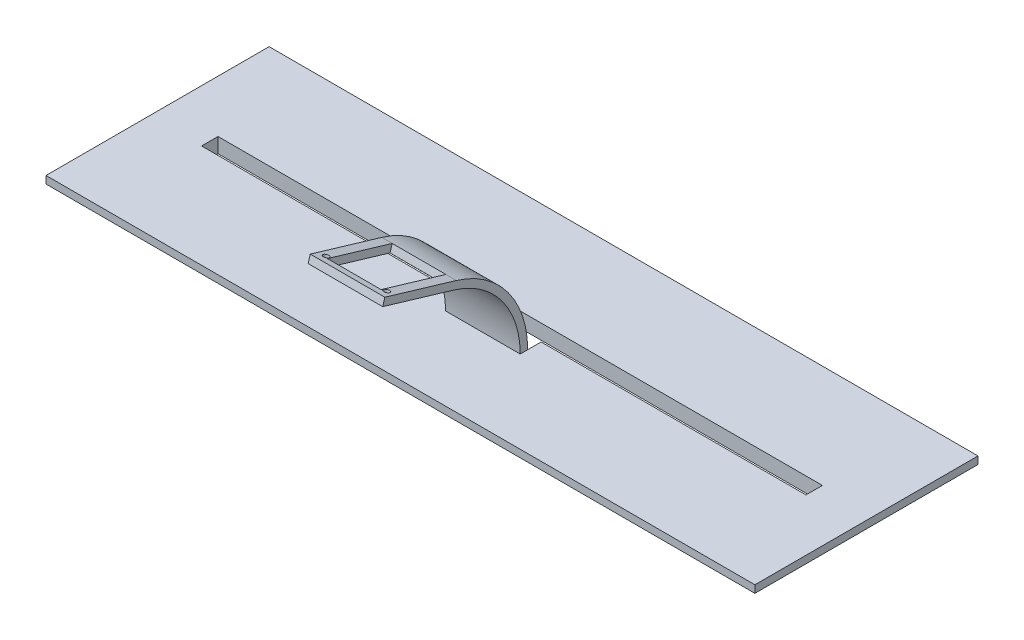
SolidWorks part; units mm, degrees
ref_plane "Front" through (0, 0, 0) normal (0, 0, 1) x (1, 0, 0)
ref_plane "Top" through (0, 0, 0) normal (0, 1, 0) x (1, 0, 0)
ref_plane "Right" through (0, 0, 0) normal (1, 0, 0) x (0, 0, -1)
sketch "Sketch1" plane through (0, 0, 0) normal (0, 1, 0) x (1, 0, 0)
  line L1 (-117.475, 34.798) -> (117.475, 34.798)
  line L2 (-117.475, 34.798) -> (-117.475, -34.798)
  line L3 (-117.475, -34.798) -> (117.475, -34.798)
  line L4 (117.475, 34.798) -> (117.475, -34.798)
  line L5 (-117.475, 34.798) -> (117.475, -34.798) construction
  line L6 (-117.475, -34.798) -> (117.475, 34.798) construction
  point P0 (0, 0)
  dimension "D1" = 69.596
  dimension "D2" = 234.95
extrude "Boss-Extrude1" add sketch "Sketch1" along normal blind 2.54
sketch "Sketch2" plane through (0, 2.54, 0) normal (0, 1, 0) x (1, 0, 0)
  line L8 (120.65, -37.973) -> (120.65, 37.973)
  line L9 (120.65, 37.973) -> (-120.65, 37.973)
  line L10 (-120.65, 37.973) -> (-120.65, -37.973)
  line L11 (-120.65, -37.973) -> (120.65, -37.973)
  line L12 (120.65, -37.973) -> (120.65, 37.973)
  line L13 (120.65, 37.973) -> (-120.65, 37.973)
  line L14 (-120.65, 37.973) -> (-120.65, -37.973)
  line L15 (-120.65, -37.973) -> (120.65, -37.973)
  dimension "D1" = 3.175
extrude "Boss-Extrude2" add sketch "Sketch2" along normal blind 2.54
sketch "Sketch3" plane through (0, 5.08, 0) normal (0, 1, 0) x (1, 0, 0)
  line L1 (-102.87, 2.794) -> (102.87, 2.794)
  line L2 (-102.87, 2.794) -> (-102.87, -7.366)
  line L3 (-102.87, -7.366) -> (102.87, -7.366)
  line L4 (102.87, 2.794) -> (102.87, -7.366)
  line L5 (120.65, 37.973) -> (-120.65, 37.973) construction
  line L6 (-12.7, -2.794) -> (-12.7, -7.366)
  line L7 (-102.87, -2.794) -> (102.87, -2.794)
  line L8 (-102.87, -2.794) -> (-102.87, 2.794)
  line L9 (-102.87, 2.794) -> (102.87, 2.794)
  line L10 (102.87, -2.794) -> (102.87, 2.794)
  line L11 (-102.87, -2.794) -> (102.87, 2.794) construction
  line L12 (-102.87, 2.794) -> (102.87, -2.794) construction
  line L13 (0, -31.2408) -> (0, 31.2408) construction
  line L14 (12.7, -2.794) -> (12.7, -7.366)
  point P0 (0, 0)
  point P8 (0, 0)
  dimension "D1" = 205.74
  dimension "D2" = 10.16
  dimension "D3" = 35.179
  dimension "D4" = 25.4
extrude "Cut-Extrude2" cut sketch "Sketch3" against normal through all contours L2 L7 L4 L1 | L14 L7 L6 L3 region at (0, 5.08, 0) region at (0, 5.08, 5.08)
sketch "Sketch4" plane through (0, 0, 0) normal (1, 0, 0) x (0, 0, -1)
  line L0 (2.794, 5.08) -> (-2.794, 5.08) construction
  line L1 (2.794, 5.08) -> (-2.794, 5.08)
  line L2 (-31.6329, 37.626) -> (-32.3578, 35.1916)
  line L4 (-37.973, 2.54) -> (37.973, 2.54)
  line L5 (37.973, 2.54) -> (37.973, 5.08)
  line L6 (37.973, 5.08) -> (-37.973, 5.08)
  line L7 (-37.973, 5.08) -> (-37.973, 2.54)
  line L8 (-37.973, 2.54) -> (37.973, 2.54)
  line L9 (37.973, 2.54) -> (37.973, 5.08)
  line L10 (37.973, 5.08) -> (-37.973, 5.08)
  line L11 (-37.973, 5.08) -> (-37.973, 2.54)
  line L14 (-2.794, 5.08) -> (-7.366, 5.08)
  line L15 (-7.366, 5.08) -> (-7.366, 0)
  line L16 (-7.366, 0) -> (-2.794, 0)
  line L17 (-2.794, 0) -> (-2.794, 5.08)
  line L18 (-2.794, 5.08) -> (-7.366, 5.08)
  line L19 (-7.366, 5.08) -> (-7.366, 0)
  line L20 (-7.366, 0) -> (-2.794, 0)
  line L21 (-2.794, 0) -> (-2.794, 5.08)
  arc A0 (-7.366, 5.08) -> (-31.6329, 37.626) centre (-41.3243, 5.08) ccw
  arc A1 (-9.906, 5.08) -> (-32.3578, 35.1916) centre (-41.3243, 5.08) ccw
  dimension "D1" = 0
  dimension "D2" = 0
  dimension "D3" = 2.54
extrude "Boss-Extrude7" add sketch "Sketch4" along normal blind 12.7 and the other way blind 12.7 contours A1 L10 A0 L2 region at (0, 5.4903, 8.636)
sketch "Sketch5" plane through (0, 11.7168, 39.348) normal (0, 0.2854, 0.9584) x (1, 0, 0)
  line L4 (-12.7, 24.4935) -> (12.7, 24.4935)
  line L5 (12.7, 24.4935) -> (12.7, 27.0335)
  line L6 (12.7, 27.0335) -> (-12.7, 27.0335)
  line L7 (-12.7, 27.0335) -> (-12.7, 24.4935)
  line L8 (-12.7, 24.4935) -> (12.7, 24.4935)
  line L9 (12.7, 24.4935) -> (12.7, 27.0335)
  line L10 (12.7, 27.0335) -> (-12.7, 27.0335)
  line L11 (-12.7, 27.0335) -> (-12.7, 24.4935)
  dimension "D1" = 0
extrude "Boss-Extrude8" add sketch "Sketch5" along normal blind 25.4
sketch "Sketch6" plane through (0, 25.9092, -7.7151) normal (0, 0.9584, -0.2854) x (1, 0, 0)
  line L0 (0, -31.2408) -> (0, 31.2408) construction
  line L1 (-9.144, -41.0554) -> (9.144, -41.0554)
  line L2 (-9.144, -41.0554) -> (-9.144, -64.0742)
  line L3 (-9.144, -64.0742) -> (9.144, -64.0742)
  line L4 (12.7, -41.0554) -> (-12.7, -41.0554)
  line L5 (-12.7, -41.0554) -> (-12.7, -66.4554)
  line L6 (-12.7, -66.4554) -> (12.7, -66.4554)
  line L7 (12.7, -66.4554) -> (12.7, -41.0554)
  line L8 (12.7, -41.0554) -> (-12.7, -41.0554)
  line L9 (-12.7, -41.0554) -> (-12.7, -66.4554)
  line L10 (-12.7, -66.4554) -> (12.7, -66.4554)
  line L11 (12.7, -66.4554) -> (12.7, -41.0554)
  line L12 (9.144, -41.0554) -> (9.144, -64.0742)
  line L13 (-9.144, -41.0554) -> (9.144, -64.0742) construction
  line L14 (-9.144, -64.0742) -> (9.144, -41.0554) construction
  point P2 (0, -52.5648)
  dimension "D2" = 18.288
  dimension "D3" = 23.0188
  dimension "D1" = 0
extrude "Cut-Extrude3" cut sketch "Sketch6" against normal up to next contours L12 L1 L2 L3 region at (0, 40.9107, 42.6636)
sketch "Sketch9" plane through (0, 25.9092, -7.7151) normal (0, 0.9584, -0.2854) x (1, 0, 0)
  line L0 (0, -31.2408) -> (0, 31.2408) construction
  line L1 (9.144, -41.0554) -> (-9.144, -41.0554) construction
  circle A0 centre (-10.3187, -63.2804) radius 1
  circle A1 centre (10.3187, -63.2804) radius 1
  dimension "D3" = 2
  dimension "D1" = 22.225
  dimension "D2" = 20.6375
extrude "Cut-Extrude4" cut sketch "Sketch9" against normal up to next
